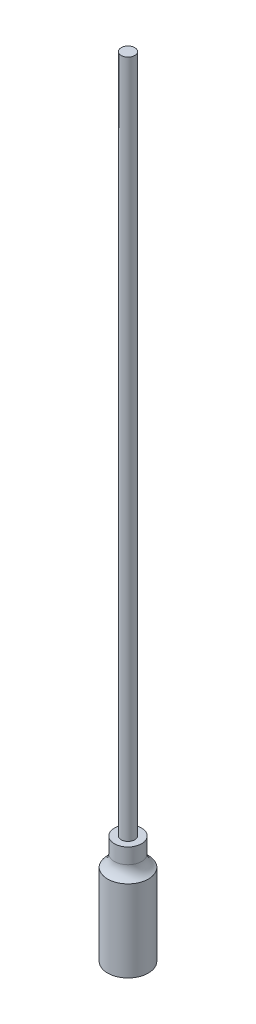
SolidWorks part; units mm, degrees
ref_plane "Front Plane" through (0, 0, 0) normal (0, 0, 1) x (1, 0, 0)
ref_plane "Top Plane" through (0, 0, 0) normal (0, 1, 0) x (1, 0, 0)
ref_plane "Right Plane" through (0, 0, 0) normal (1, 0, 0) x (0, 0, -1)
sketch "Sketch1" plane through (0, 0, 0) normal (0, 1, 0) x (1, 0, 0)
  circle A0 centre (0, 0) radius 1.5
  dimension "D1" = 3
extrude "Boss-Extrude1" add sketch "Sketch1" along normal blind 6
sketch "Sketch2" plane through (0, 6, 0) normal (0, 1, 0) x (1, 0, 0)
  circle A0 centre (0, 0) radius 1
  dimension "D1" = 2
extrude "Boss-Extrude2" add sketch "Sketch2" along normal blind 2
fillet "Fillet1" radius 1 1 edges at (0, 6, 1)
sketch "Sketch3" plane through (0, 8, 0) normal (0, 1, 0) x (1, 0, 0)
  circle A0 centre (0, 0) radius 0.5
  dimension "D1" = 1
extrude "Boss-Extrude3" add sketch "Sketch3" along normal blind 50
